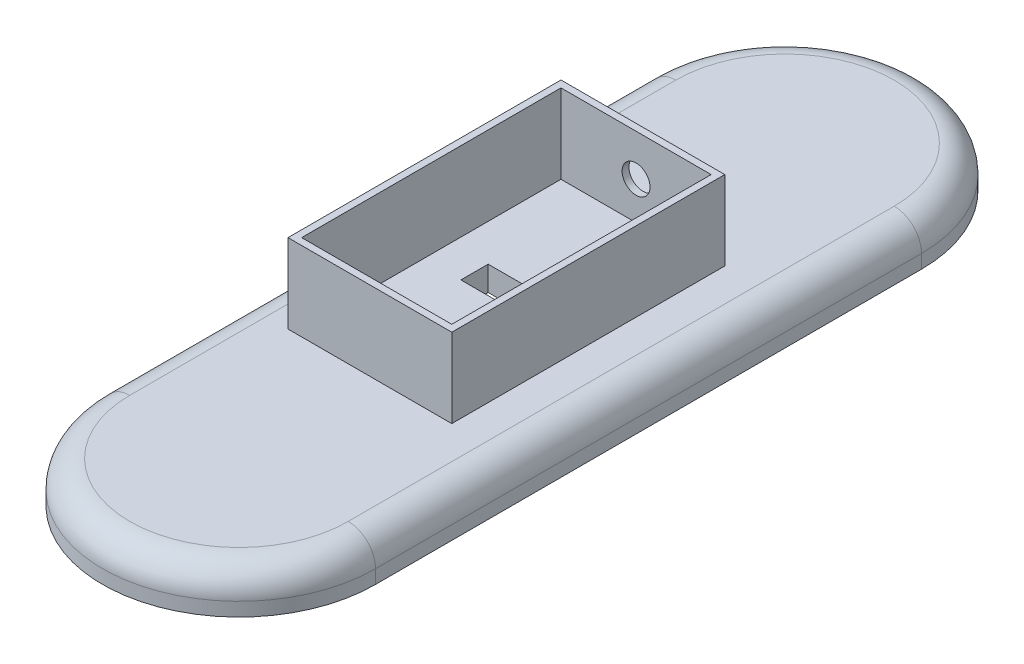
SolidWorks part; units mm, degrees
ref_plane "Plan de face" through (0, 0, 0) normal (0, 0, 1) x (1, 0, 0)
ref_plane "Plan de dessus" through (0, 0, 0) normal (0, 1, 0) x (1, 0, 0)
ref_plane "Plan de droite" through (0, 0, 0) normal (1, 0, 0) x (0, 0, -1)
sketch "Esquisse1" plane through (0, 0, 0) normal (0, 1, 0) x (1, 0, 0)
  line L1 (-50.8584, 46.306) -> (49.1416, 46.306)
  line L2 (-50.8584, 46.306) -> (-50.8584, -153.694)
  line L3 (-50.8584, -153.694) -> (49.1416, -153.694)
  line L4 (49.1416, 46.306) -> (49.1416, -153.694)
  line L5 (-45.8584, -153.694) -> (44.1416, -153.694)
  line L6 (-45.8584, -153.694) -> (-45.8584, 46.306)
  line L7 (-45.8584, 46.306) -> (44.1416, 46.306)
  line L8 (44.1416, -153.694) -> (44.1416, 46.306)
  line L9 (-32.9155, -3.694) -> (27.0845, -3.694)
  line L10 (-32.9155, -3.694) -> (-32.9155, -103.694)
  line L11 (-32.9155, -103.694) -> (27.0845, -103.694)
  line L12 (27.0845, -3.694) -> (27.0845, -103.694)
  line L13 (24.5845, -101.194) -> (-30.4155, -101.194)
  line L14 (24.5845, -101.194) -> (24.5845, -6.194)
  line L15 (24.5845, -6.194) -> (-30.4155, -6.194)
  line L16 (-30.4155, -101.194) -> (-30.4155, -6.194)
  line L17 (8.1709, -56.4517) -> (-16.8291, -56.4517)
  line L18 (8.1709, -56.4517) -> (8.1709, -46.4517)
  line L19 (8.1709, -46.4517) -> (-16.8291, -46.4517)
  line L20 (-16.8291, -56.4517) -> (-16.8291, -46.4517)
  line L21 (-21.8291, -62.7622) -> (13.1709, -62.7622)
  line L22 (-21.8291, -62.7622) -> (-21.8291, -40.1908)
  line L23 (-21.8291, -40.1908) -> (13.1709, -40.1908)
  line L24 (13.1709, -62.7622) -> (13.1709, -40.1908)
  line L25 (-26.8291, -67.0971) -> (18.1709, -67.0971)
  line L26 (-26.8291, -67.0971) -> (-26.8291, -35.8559)
  line L27 (-26.8291, -35.8559) -> (18.1709, -35.8559)
  line L28 (18.1709, -67.0971) -> (18.1709, -35.8559)
  circle A0 centre (-0.8584, 46.306) radius 50
  circle A1 centre (-0.8584, -153.694) radius 50
  circle A2 centre (-0.8584, -153.694) radius 45
  circle A3 centre (-0.8584, 46.306) radius 45
  point P34 (-21.8291, -51.4765)
  dimension "D3" = 200
  dimension "D1" = 100
  dimension "D2" = 200
  dimension "D4" = 50
  dimension "D5" = 50
  dimension "D6" = 60
  dimension "D7" = 2.5
  dimension "D8" = 2.5
  dimension "D9" = 2.5
  dimension "D10" = 2.5
  dimension "D11" = 10
  dimension "D12" = 25
  dimension "D13" = 5
  dimension "D14" = 5
  dimension "D15" = 5
  dimension "D16" = 5
extrude "Boss.-Extru.2" add sketch "Esquisse1" along normal blind 15 contours A0 | L4 L3 L2 L1 | A1
fillet "Congé3" radius 10 4 edges at (-0.8584, 15, -96.306) (-50.8584, 15, 53.694) (-0.8584, 15, 203.694) (49.1416, 15, 53.694) type face fillet first side face at (-0.8584, 15, 53.694) second side face at (-50.8584, 7.5, 53.694) second side face at (-0.8584, 7.5, -71.306) second side face at (49.1416, 7.5, 53.694) second side face at (-0.8584, 7.5, 178.694)
sketch "Esquisse3" plane through (0, 0, 0) normal (0, 1, 0) x (1, 0, 0)
extrude "Enlèv. mat.-Extru.6" cut sketch "Esquisse1<5>" along normal blind 6 contours L1 A3 | L3 A2 | L3 A2 | L8 L7 L6 L5 region at (-0.8584, 0, -65.4046) region at (-0.8584, 0, 134.5954) region at (-0.8584, 0, 172.7926)
sketch "Esquisse1<5>" plane through (0, 0, 0) normal (0, 1, 0) x (1, 0, 0) same geometry as "Esquisse1"
sketch "Esquisse4" plane through (0, 0, 0) normal (0, 1, 0) x (1, 0, 0)
extrude "Boss.-Extru.3" add sketch "Esquisse1<6>" along normal blind 44 and the other way blind 0.5 contours L12 L9 L10 L11 region at (13.113, 0, 4.8602)
sketch "Esquisse1<6>" plane through (0, 0, 0) normal (0, 1, 0) x (1, 0, 0) same geometry as "Esquisse1"
sketch "Esquisse5" plane through (0, 0, 0) normal (0, 1, 0) x (1, 0, 0)
extrude "Enlèv. mat.-Extru.7" cut sketch "Esquisse1<10>" along normal blind 90 and the other way blind 131 contours L20 L17 L18 L19 region at (-4.3291, 0, 51.4517)
sketch "Esquisse1<10>" plane through (0, 0, 0) normal (0, 1, 0) x (1, 0, 0) same geometry as "Esquisse1"
sketch "Esquisse6" plane through (0, 0, 0) normal (0, 0, 1) x (1, 0, 0)
  line L0 (-32.9155, 15) -> (-32.9155, 44) construction
  circle A0 centre (-2.9155, 28.8133) radius 5.1188
  point P2 (0, 28.8133)
  dimension "D1" = 30
extrude "Enlèv. mat.-Extru.8" cut sketch "Esquisse6" along normal blind 13
